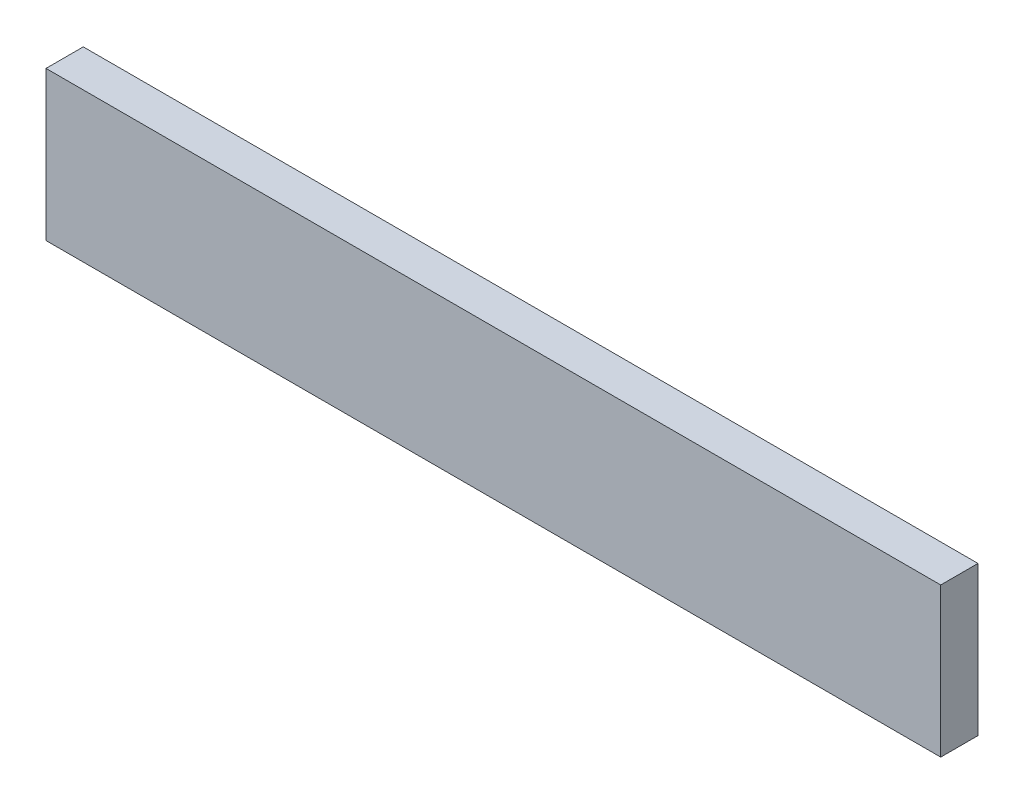
SolidWorks part; units mm, degrees
ref_plane "Front Plane" through (0, 0, 0) normal (0, 0, 1) x (1, 0, 0)
ref_plane "Top Plane" through (0, 0, 0) normal (0, 1, 0) x (1, 0, 0)
ref_plane "Right Plane" through (0, 0, 0) normal (1, 0, 0) x (0, 0, -1)
sketch "Sketch1" plane through (0, 0, 0) normal (0, 0, 1) x (1, 0, 0)
  line L1 (-152.4, -25.4) -> (152.4, -25.4)
  line L2 (-152.4, -25.4) -> (-152.4, 25.4)
  line L3 (-152.4, 25.4) -> (152.4, 25.4)
  line L4 (152.4, -25.4) -> (152.4, 25.4)
  line L5 (-152.4, -25.4) -> (152.4, 25.4) construction
  line L6 (-152.4, 25.4) -> (152.4, -25.4) construction
  point P0 (0, 0)
  dimension "D1" = 304.8
  dimension "D2" = 50.8
extrude "Boss-Extrude1" add sketch "Sketch1" along normal blind 12.7 contours L1 L3 region at (0, 0, 0)
